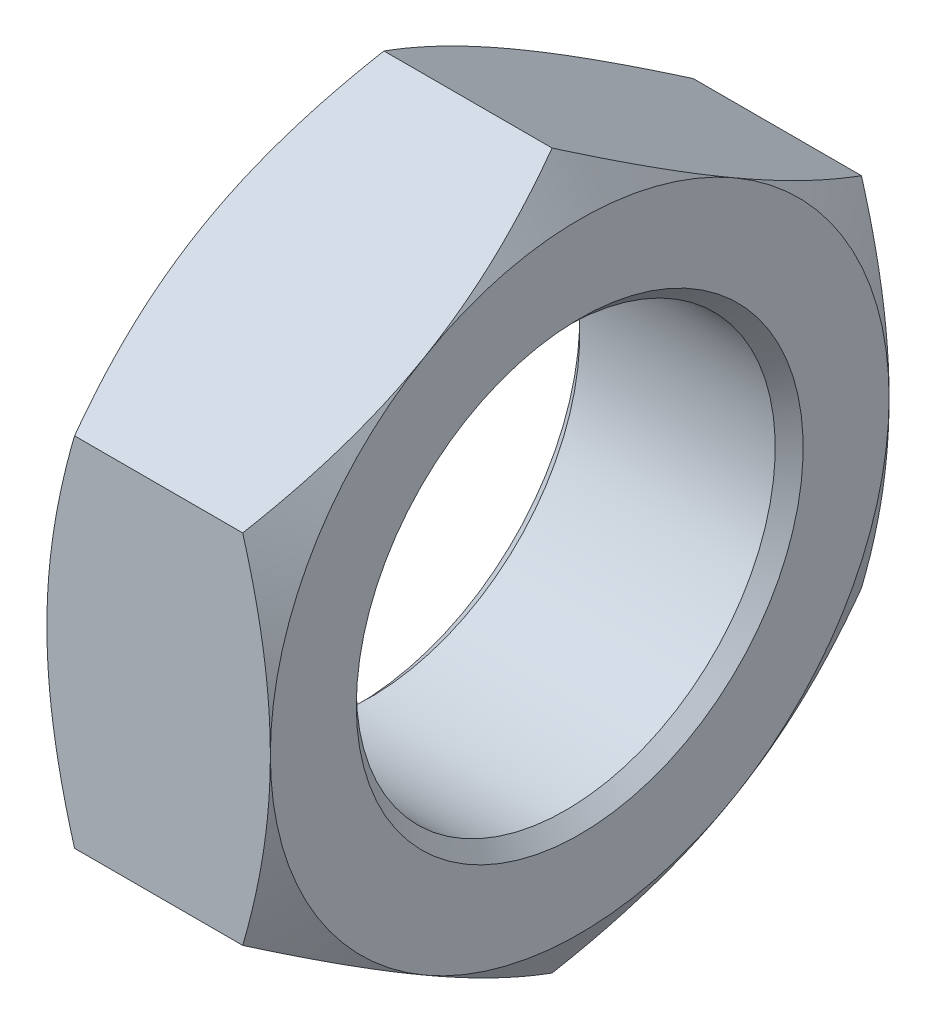
SolidWorks part; units mm, degrees
material "A3钢"
ref_plane "前视基准面" through (0, 0, 0) normal (0, 0, 1) x (1, 0, 0)
ref_plane "上视基准面" through (0, 0, 0) normal (0, 1, 0) x (1, 0, 0)
ref_plane "右视基准面" through (0, 0, 0) normal (1, 0, 0) x (0, 0, -1)
sketch "草图1" plane through (0, 0, 0) normal (0, 0, 1) x (1, 0, 0)
  line L0 (0, 0) -> (0, 18)
  line L1 (0, 18) -> (2.0785, 21.6)
  line L2 (2.0785, 21.6) -> (10.9215, 21.6)
  line L3 (10.9215, 21.6) -> (13, 18)
  line L4 (13, 18) -> (13, 0)
  line L5 (13, 0) -> (0, 0)
  line L6 (13, 0) -> (0, 0) construction
revolve "旋转1" add sketch "草图1" angle 360 about L6 reverse direction yes
sketch "草图2" plane through (0, 0, 0) normal (1, 0, 0) x (0, 0, -1)
  line L0 (-36, 36) -> (-36, -36)
  line L1 (-36, -36) -> (36, -36)
  line L2 (36, -36) -> (36, 36)
  line L3 (36, 36) -> (-36, 36)
  line L4 (-18, -10.3923) -> (0, -20.7846)
  line L5 (0, -20.7846) -> (18, -10.3923)
  line L6 (18, -10.3923) -> (18, 10.3923)
  line L7 (18, 10.3923) -> (0, 20.7846)
  line L8 (0, 20.7846) -> (-18, 10.3923)
  line L9 (-18, 10.3923) -> (-18, -10.3923)
extrude "切除-拉伸1" cut sketch "草图2" along normal blind 26
sketch "草图3" plane through (0, 0, 0) normal (0, 0, 1) x (1, 0, 0)
  line L0 (0, 0) -> (0, 13)
  line L1 (0, 13) -> (0.812, 12.188)
  line L2 (0.812, 12.188) -> (12.188, 12.188)
  line L3 (12.188, 12.188) -> (13, 13)
  line L4 (13, 13) -> (13, 0)
  line L5 (13, 0) -> (0, 0)
  line L6 (13, 0) -> (0, 0) construction
revolve "切除-旋转1" cut sketch "草图3" angle 360 about L6 reverse direction yes
cosmetic thread "装饰螺纹线1" parameters "D1"=13, "D2"=26
ref_plane "基准面1" through (6.5, 0, 0) normal (1, 0, 0) x (0, 0, -1)
ref_plane "IP_RN XY" through (6.5, 0, 0) normal (1, 0, 0) x (0, 0, -1)
ref_plane "IP_RN XZ" through (0, 0, 0) normal (0, -1, 0) x (-1, 0, 0)
ref_plane "IP_RN YZ" through (0, 0, 0) normal (0, 0, -1) x (-1, 0, 0)
ref_axis "IP_RN X" through (6.5, 0, 80.9) along (0, 0, -1)
ref_axis "IP_RN Y" through (6.5, -50, 0) along (0, 1, 0)
ref_axis "IP_RN Z" through (80.9, 0, 0) along (-1, 0, 0)
sketch3d "IP_RN"
  point P0 (6.5, 0, 0)
